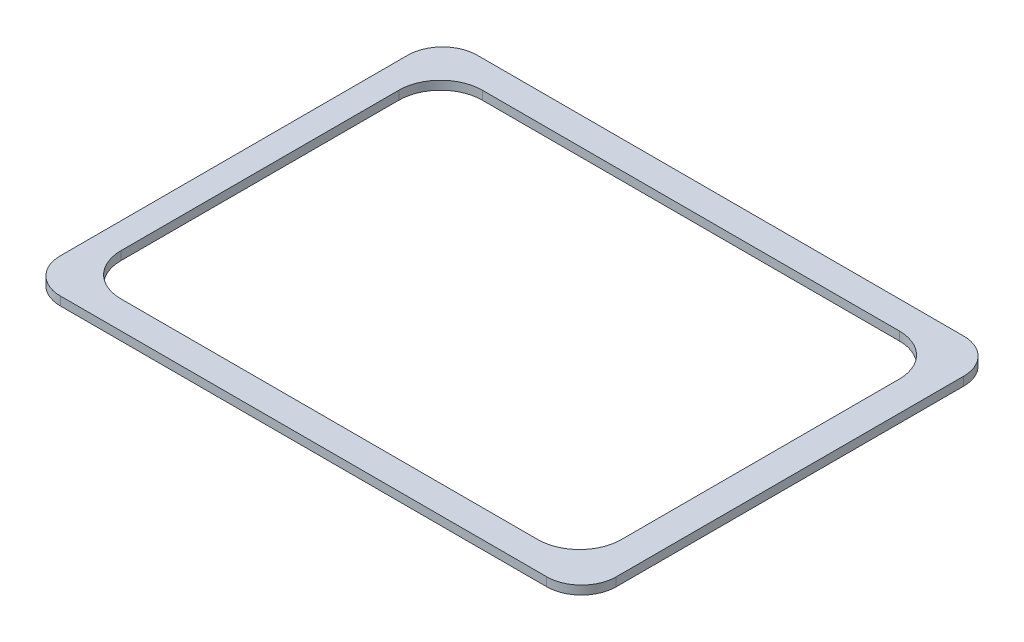
SolidWorks part; units mm, degrees
ref_plane "Front Plane" through (0, 0, 0) normal (0, 0, 1) x (1, 0, 0)
ref_plane "Top Plane" through (0, 0, 0) normal (0, 1, 0) x (1, 0, 0)
ref_plane "Right Plane" through (0, 0, 0) normal (1, 0, 0) x (0, 0, -1)
sketch "Sketch1" plane through (0, 6.35, 0) normal (0, 1, 0) x (1, 0, 0)
  line L19 (90.75, -50.8) -> (90.75, 0)
  line L24 (90.75, 0) -> (90.75, 50.8)
  line L25 (75.5, 66.05) -> (-76.9, 66.05)
  line L26 (-92.15, 50.8) -> (-92.15, -50.8)
  line L27 (-76.9, -66.05) -> (75.5, -66.05)
  line L28 (90.75, -50.8) -> (90.75, 0)
  line L29 (90.75, 0) -> (90.75, 50.8)
  line L30 (75.5, 66.05) -> (-76.9, 66.05)
  line L31 (-92.15, 50.8) -> (-92.15, -50.8)
  line L32 (-76.9, -66.05) -> (75.5, -66.05)
  line L44 (101.6, -63.5) -> (101.6, 63.5) construction
  line L45 (88.9, 76.2) -> (-88.9, 76.2) construction
  line L46 (-101.6, 63.5) -> (-101.6, -63.5) construction
  line L47 (-88.9, -76.2) -> (88.9, -76.2) construction
  line L52 (101.6, -63.5) -> (101.6, 63.5)
  line L53 (88.9, 76.2) -> (-88.9, 76.2)
  line L54 (-101.6, 63.5) -> (-101.6, -63.5)
  line L55 (-88.9, -76.2) -> (88.9, -76.2)
  arc A4 (88.9, -76.2) -> (101.6, -63.5) centre (88.9, -63.5) ccw construction
  arc A6 (101.6, 63.5) -> (88.9, 76.2) centre (88.9, 63.5) ccw construction
  arc A8 (-88.9, 76.2) -> (-101.6, 63.5) centre (-88.9, 63.5) ccw construction
  arc A10 (-101.6, -63.5) -> (-88.9, -76.2) centre (-88.9, -63.5) ccw construction
  arc A16 (88.9, -76.2) -> (101.6, -63.5) centre (88.9, -63.5) ccw
  arc A17 (101.6, 63.5) -> (88.9, 76.2) centre (88.9, 63.5) ccw
  arc A18 (-88.9, 76.2) -> (-101.6, 63.5) centre (-88.9, 63.5) ccw
  arc A19 (-101.6, -63.5) -> (-88.9, -76.2) centre (-88.9, -63.5) ccw
  arc A24 (90.75, 50.8) -> (75.5, 66.05) centre (75.5, 50.8) ccw
  arc A25 (-76.9, 66.05) -> (-92.15, 50.8) centre (-76.9, 50.8) ccw
  arc A26 (-92.15, -50.8) -> (-76.9, -66.05) centre (-76.9, -50.8) ccw
  arc A27 (75.5, -66.05) -> (90.75, -50.8) centre (75.5, -50.8) ccw
  arc A28 (90.75, 50.8) -> (75.5, 66.05) centre (75.5, 50.8) ccw
  arc A29 (-76.9, 66.05) -> (-92.15, 50.8) centre (-76.9, 50.8) ccw
  arc A30 (-92.15, -50.8) -> (-76.9, -66.05) centre (-76.9, -50.8) ccw
  arc A31 (75.5, -66.05) -> (90.75, -50.8) centre (75.5, -50.8) ccw
  dimension "D1" = 3
extrude "FrontFace" add sketch "Sketch1" along normal blind 3.175
equation "\"ShellWallThickness\"=0.115"
equation "\"ShellOverlap\"=0.625"
